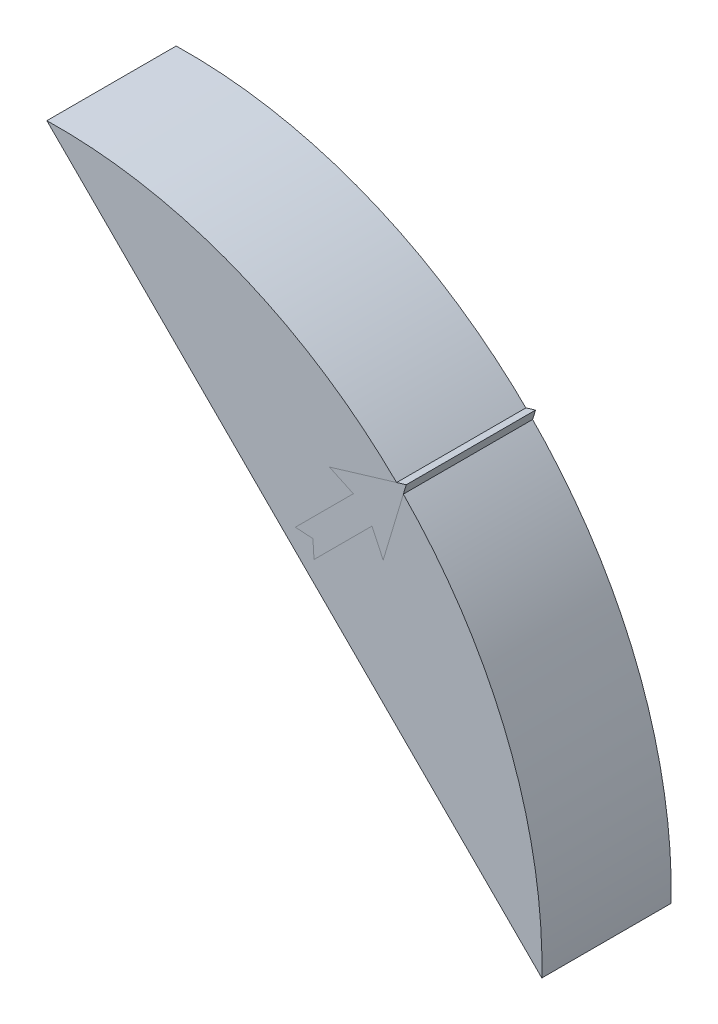
SolidWorks part; units mm, degrees
note: The reader was unsure of these and kept them because the rebuilt part matched: shared geometry of "Sketch1<3>", "Sketch1<4>", "Sketch1<5>", "main_features_sketch<6>".
ref_plane "Front Plane" through (0, 0, 0) normal (0, 0, 1) x (1, 0, 0)
ref_plane "Top Plane" through (0, 0, 0) normal (0, 1, 0) x (1, 0, 0)
ref_plane "Right Plane" through (0, 0, 0) normal (1, 0, 0) x (0, 0, -1)
sketch "main_features_sketch" plane through (0, 0, 0) normal (0, 0, 1) x (1, 0, 0)
  line L0 (0, 0) -> (38.9517, 38.9517) construction
  line L1 (0.8016, 53.0799) -> (53.0799, 0.8016)
  line L2 (55.0731, -1.1916) -> (53.0799, 0.8016)
  line L3 (-1.1916, 55.0731) -> (0.8016, 53.0799)
  line L4 (-80.8223, 134.7038) -> (134.7038, -80.8223) construction
  line L5 (27.0561, 29.1774) -> (33.6484, 35.7697)
  line L6 (33.6484, 35.7697) -> (30.9295, 37.0376)
  line L7 (30.9295, 37.0376) -> (39.6588, 39.6588)
  line L11 (29.0522, 29.0522) -> (27.0561, 29.1774)
  line L12 (38.9517, 38.9517) -> (39.6588, 39.6588) construction
  line L13 (29.0522, 29.0522) -> (29.1774, 27.0561)
  line L14 (37.0376, 30.9295) -> (39.6588, 39.6588)
  line L15 (35.7697, 33.6484) -> (37.0376, 30.9295)
  line L16 (29.1774, 27.0561) -> (35.7697, 33.6484)
  line L25 (33.6484, 35.7697) -> (35.7697, 33.6484) construction
  arc A0 (0.8016, 53.0799) -> (53.0799, 0.8016) centre (0, 0) cw
  arc A1 (-1.1916, 55.0731) -> (55.0731, -1.1916) centre (0, 0) cw
  circle A2 centre (0, 0) radius 53.086 construction
  point P8 (32.0583, 32.0583)
  point P10 (37.5375, 37.5375)
  point P15 (17.9605, 17.9605)
  dimension "D1" = 2
  dimension "D2" = 1
  dimension "D3" = 3
  dimension "D4" = 15
  dimension "D5" = 70
  dimension "D6" = 3
  dimension "D7" = 7
  dimension "D8" = 2
extrude "face" add sketch "main_features_sketch" along normal blind 2 contours A0 L1 L14 L15 L16 L13 L11 L5 L6 L7 | A1 L14 A0 L2 | A1 L7 A0 L14 | A1 L3 A0 L7 | A0 L7 L6 L5 L11 L13 L16 L15 L14
extrude "curved_alignment" add sketch "Sketch1<3>" against normal blind 12.7 contours A1 L3 A0 L7 | A1 L7 A0 L14 | A1 L14 A0 L2
sketch "Sketch1<3>" plane through (0, 0, 0) normal (0, 0, 1) x (1, 0, 0) same geometry as "main_features_sketch"
extrude "arrow_cut" cut sketch "Sketch1<4>" against normal blind 0.5 from surface contours A0 L5 L11 L13 L16 | A1 L7 L6 L5 A0 L16 L15 L14 | L7 A1 L14
sketch "Sketch1<4>" plane through (0, 0, 0) normal (0, 0, 1) x (1, 0, 0) same geometry as "main_features_sketch"
extrude "arrow_extrude" add sketch "Sketch1<5>" against normal blind 0.5 from surface separate body contours A0 L5 L11 L13 L16 | A1 L7 L6 L5 A0 L16 L15 L14 | L7 A1 L14
sketch "Sketch1<5>" plane through (0, 0, 0) normal (0, 0, 1) x (1, 0, 0) same geometry as "main_features_sketch"
extrude "arrow_tip" add sketch "main_features_sketch<6>" against normal up to surface and the other way up to next contours L7 A1 L14
sketch "main_features_sketch<6>" plane through (0, 0, 0) normal (0, 0, 1) x (1, 0, 0) same geometry as "main_features_sketch"
